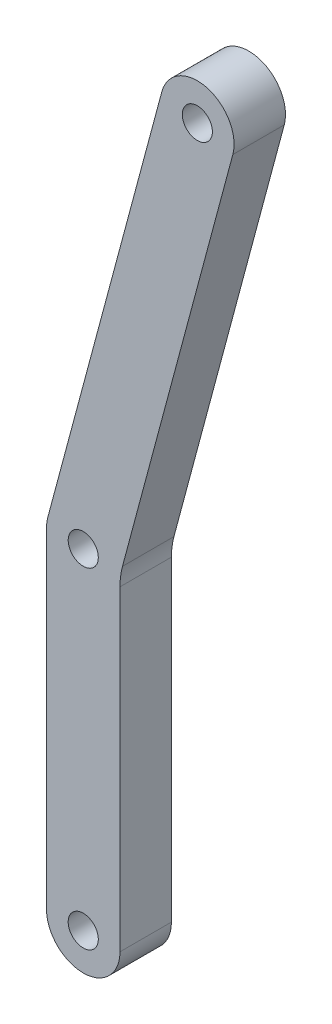
SolidWorks part; units mm, degrees
ref_plane "Plan de face" through (0, 0, 0) normal (0, 0, 1) x (1, 0, 0)
ref_plane "Plan de dessus" through (0, 0, 0) normal (0, 1, 0) x (1, 0, 0)
ref_plane "Plan de droite" through (0, 0, 0) normal (1, 0, 0) x (0, 0, -1)
sketch "Esquisse1" plane through (0, 0, 0) normal (0, 0, 1) x (1, 0, 0)
  line L0 (0, 0) -> (0, 45) construction
  line L1 (-5, 0) -> (-5, 45)
  line L2 (5, 0) -> (5, 45)
  line L3 (0, 45) -> (15.5291, 102.9555) construction
  line L4 (-4.8296, 46.2941) -> (10.6995, 104.2496)
  line L5 (4.8296, 43.7059) -> (20.3588, 101.6615)
  arc A0 (-5, 0) -> (5, 0) centre (0, 0) ccw
  arc A1 (5, 45) -> (-5, 45) centre (0, 45) ccw
  arc A2 (-4.8296, 46.2941) -> (4.8296, 43.7059) centre (0, 45) ccw
  arc A3 (20.3588, 101.6615) -> (10.6995, 104.2496) centre (15.5291, 102.9555) ccw
  circle A4 centre (0, 0) radius 2.05
  circle A5 centre (0, 45) radius 2.05
  circle A6 centre (15.5291, 102.9555) radius 2.05
  point P3 (0, 22.5)
  point P8 (7.7646, 73.9778)
  dimension "D5" = 4.1
  dimension "D6" = 4.1
  dimension "D7" = 4.1
  dimension "D1" = 60
  dimension "D2" = 45
  dimension "D3" = 165
  dimension "D4" = 10
extrude "Boss.-Extru.1" add sketch "Esquisse1" along normal blind 7 contours L5 A3 L4 A1 L2 A6 | A1 A2 L5 L2 A5 | A2 L1 A0 L2 L5 A4 region at (-0.0002, 19.1333, 0) region at (-4.817, 45.6342, 0) region at (8.6292, 77.2054, 0)
fillet "Congé1" radius 10 1 edges at (5, 44.3417, 3.5)
